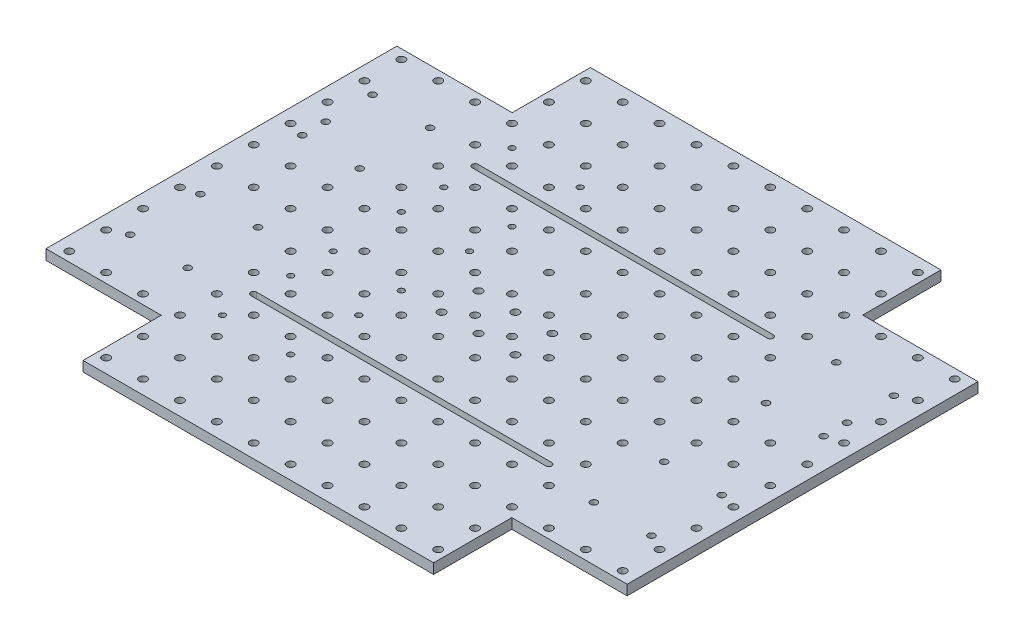
SolidWorks part; units mm, degrees
ref_plane "Front Plane" through (0, 0, 0) normal (0, 0, 1) x (1, 0, 0)
ref_plane "Top Plane" through (0, 0, 0) normal (0, 1, 0) x (1, 0, 0)
ref_plane "Right Plane" through (0, 0, 0) normal (1, 0, 0) x (0, 0, -1)
sketch "Sketch1" plane through (0, 0, 0) normal (0, 1, 0) x (1, 0, 0)
  line L0 (95, -95.1) -> (157.5, -95.1)
  line L1 (-157.5, 95.1) -> (-95, 95.1)
  line L2 (-157.5, 95.1) -> (-157.5, -95.1)
  line L3 (-157.5, -95.1) -> (-95, -95.1)
  line L4 (157.5, 95.1) -> (157.5, -95.1)
  line L5 (-157.5, 95.1) -> (157.5, -95.1) construction
  line L6 (-157.5, -95.1) -> (157.5, 95.1) construction
  line L7 (95, 137.5) -> (-95, 137.5)
  line L8 (95, 137.5) -> (95, 95.1)
  line L9 (95, -137.5) -> (-95, -137.5)
  line L10 (-95, 137.5) -> (-95, 95.1)
  line L11 (95, 137.5) -> (-95, -137.5) construction
  line L12 (95, -137.5) -> (-95, 137.5) construction
  line L13 (95, -95.1) -> (95, -137.5)
  line L14 (-95, -95.1) -> (-95, -137.5)
  line L15 (95, 95.1) -> (157.5, 95.1)
  point P0 (0, 0)
  point P6 (0, 0)
  dimension "D1" = 315
  dimension "D2" = 42.4
  dimension "D3" = 275
  dimension "D4" = 190
extrude "Boss-Extrude1" add sketch "Sketch1" along normal blind 5.4864
sketch "Sketch2" plane through (0, 5.4864, 0) normal (0, 1, 0) x (1, 0, 0)
  line L0 (0, 0) -> (150, 0) construction
  line L1 (150, 0) -> (150, -130) construction
  line L2 (150, -130) -> (130, -130) construction
  line L3 (150, -110) -> (130, -110) construction
  line L4 (150, -90) -> (130, -90) construction
  line L5 (150, -70) -> (130, -70) construction
  line L6 (150, -50) -> (130, -50) construction
  line L7 (150, -30) -> (130, -30) construction
  line L8 (150, -10) -> (130, -10) construction
  line L9 (150, 10) -> (130, 10) construction
  line L10 (150, 30) -> (130, 30) construction
  line L11 (150, 50) -> (130, 50) construction
  line L12 (150, 70) -> (130, 70) construction
  line L13 (150, 90) -> (130, 90) construction
  line L14 (150, 110) -> (130, 110) construction
  line L15 (150, -130) -> (150, -110) construction
  line L16 (150, 130) -> (130, 130) construction
  line L17 (150, 150) -> (130, 150) construction
  circle A0 centre (150, -130) radius 2.1 construction
  circle A1 centre (130, -130) radius 2.1 construction
  circle A2 centre (110, -130) radius 2.1 construction
  circle A3 centre (90, -130) radius 2.1
  circle A4 centre (70, -130) radius 2.1
  circle A5 centre (50, -130) radius 2.1
  circle A6 centre (30, -130) radius 2.1
  circle A7 centre (10, -130) radius 2.1
  circle A8 centre (-10, -130) radius 2.1
  circle A9 centre (-30, -130) radius 2.1
  circle A10 centre (-50, -130) radius 2.1
  circle A11 centre (-70, -130) radius 2.1
  circle A12 centre (-90, -130) radius 2.1
  circle A13 centre (-110, -130) radius 2.1
  circle A14 centre (-130, -130) radius 2.1 construction
  circle A15 centre (-150, -130) radius 2.1 construction
  circle A17 centre (150, -110) radius 2.1 construction
  circle A18 centre (130, -110) radius 2.1 construction
  circle A19 centre (110, -110) radius 2.1 construction
  circle A20 centre (90, -110) radius 2.1
  circle A21 centre (70, -110) radius 2.1
  circle A22 centre (50, -110) radius 2.1
  circle A23 centre (30, -110) radius 2.1
  circle A24 centre (10, -110) radius 2.1
  circle A25 centre (-10, -110) radius 2.1
  circle A26 centre (-30, -110) radius 2.1
  circle A27 centre (-50, -110) radius 2.1
  circle A28 centre (-70, -110) radius 2.1
  circle A29 centre (-90, -110) radius 2.1
  circle A30 centre (-110, -110) radius 2.1
  circle A31 centre (-130, -110) radius 2.1 construction
  circle A32 centre (-150, -110) radius 2.1 construction
  circle A34 centre (150, -90) radius 2.1
  circle A35 centre (130, -90) radius 2.1
  circle A36 centre (110, -90) radius 2.1
  circle A37 centre (90, -90) radius 2.1
  circle A38 centre (70, -90) radius 2.1
  circle A39 centre (50, -90) radius 2.1
  circle A40 centre (30, -90) radius 2.1
  circle A41 centre (10, -90) radius 2.1
  circle A42 centre (-10, -90) radius 2.1
  circle A43 centre (-30, -90) radius 2.1
  circle A44 centre (-50, -90) radius 2.1
  circle A45 centre (-70, -90) radius 2.1
  circle A46 centre (-90, -90) radius 2.1
  circle A47 centre (-110, -90) radius 2.1
  circle A48 centre (-130, -90) radius 2.1
  circle A49 centre (-150, -90) radius 2.1
  circle A51 centre (150, -70) radius 2.1
  circle A52 centre (130, -70) radius 2.1 construction
  circle A53 centre (110, -70) radius 2.1 construction
  circle A54 centre (90, -70) radius 2.1
  circle A55 centre (70, -70) radius 2.1
  circle A56 centre (50, -70) radius 2.1
  circle A57 centre (30, -70) radius 2.1
  circle A58 centre (10, -70) radius 2.1
  circle A59 centre (-10, -70) radius 2.1
  circle A60 centre (-30, -70) radius 2.1
  circle A61 centre (-50, -70) radius 2.1
  circle A62 centre (-70, -70) radius 2.1
  circle A63 centre (-90, -70) radius 2.1
  circle A64 centre (-110, -70) radius 2.1 construction
  circle A65 centre (-130, -70) radius 2.1 construction
  circle A66 centre (-150, -70) radius 2.1
  circle A68 centre (150, -50) radius 2.1
  circle A69 centre (130, -50) radius 2.1 construction
  circle A70 centre (110, -50) radius 2.1 construction
  circle A71 centre (90, -50) radius 2.1
  circle A72 centre (70, -50) radius 2.1
  circle A73 centre (50, -50) radius 2.1
  circle A74 centre (30, -50) radius 2.1
  circle A75 centre (10, -50) radius 2.1
  circle A76 centre (-10, -50) radius 2.1
  circle A77 centre (-30, -50) radius 2.1
  circle A78 centre (-50, -50) radius 2.1
  circle A79 centre (-70, -50) radius 2.1
  circle A80 centre (-90, -50) radius 2.1
  circle A81 centre (-110, -50) radius 2.1 construction
  circle A82 centre (-130, -50) radius 2.1 construction
  circle A83 centre (-150, -50) radius 2.1
  circle A85 centre (150, -30) radius 2.1
  circle A86 centre (130, -30) radius 2.1 construction
  circle A87 centre (110, -30) radius 2.1 construction
  circle A88 centre (90, -30) radius 2.1
  circle A89 centre (70, -30) radius 2.1
  circle A90 centre (50, -30) radius 2.1
  circle A91 centre (30, -30) radius 2.1
  circle A92 centre (10, -30) radius 2.1
  circle A93 centre (-10, -30) radius 2.1
  circle A94 centre (-30, -30) radius 2.1
  circle A95 centre (-50, -30) radius 2.1
  circle A96 centre (-70, -30) radius 2.1
  circle A97 centre (-90, -30) radius 2.1
  circle A98 centre (-110, -30) radius 2.1 construction
  circle A99 centre (-130, -30) radius 2.1 construction
  circle A100 centre (-150, -30) radius 2.1
  circle A102 centre (150, -10) radius 2.1
  circle A103 centre (130, -10) radius 2.1
  circle A104 centre (110, -10) radius 2.1
  circle A105 centre (90, -10) radius 2.1
  circle A106 centre (70, -10) radius 2.1
  circle A107 centre (50, -10) radius 2.1
  circle A108 centre (30, -10) radius 2.1
  circle A109 centre (10, -10) radius 2.1
  circle A110 centre (-10, -10) radius 2.1
  circle A111 centre (-30, -10) radius 2.1
  circle A112 centre (-50, -10) radius 2.1
  circle A113 centre (-70, -10) radius 2.1
  circle A114 centre (-90, -10) radius 2.1
  circle A115 centre (-110, -10) radius 2.1
  circle A116 centre (-130, -10) radius 2.1
  circle A117 centre (-150, -10) radius 2.1
  circle A119 centre (150, 10) radius 2.1
  circle A120 centre (130, 10) radius 2.1
  circle A121 centre (110, 10) radius 2.1
  circle A122 centre (90, 10) radius 2.1
  circle A123 centre (70, 10) radius 2.1
  circle A124 centre (50, 10) radius 2.1
  circle A125 centre (30, 10) radius 2.1
  circle A126 centre (10, 10) radius 2.1
  circle A127 centre (-10, 10) radius 2.1
  circle A128 centre (-30, 10) radius 2.1
  circle A129 centre (-50, 10) radius 2.1
  circle A130 centre (-70, 10) radius 2.1
  circle A131 centre (-90, 10) radius 2.1
  circle A132 centre (-110, 10) radius 2.1
  circle A133 centre (-130, 10) radius 2.1
  circle A134 centre (-150, 10) radius 2.1
  circle A136 centre (150, 30) radius 2.1
  circle A137 centre (130, 30) radius 2.1 construction
  circle A138 centre (110, 30) radius 2.1 construction
  circle A139 centre (90, 30) radius 2.1
  circle A140 centre (70, 30) radius 2.1
  circle A141 centre (50, 30) radius 2.1
  circle A142 centre (30, 30) radius 2.1
  circle A143 centre (10, 30) radius 2.1
  circle A144 centre (-10, 30) radius 2.1
  circle A145 centre (-30, 30) radius 2.1
  circle A146 centre (-50, 30) radius 2.1
  circle A147 centre (-70, 30) radius 2.1
  circle A148 centre (-90, 30) radius 2.1
  circle A149 centre (-110, 30) radius 2.1 construction
  circle A150 centre (-130, 30) radius 2.1 construction
  circle A151 centre (-150, 30) radius 2.1
  circle A153 centre (150, 50) radius 2.1
  circle A154 centre (130, 50) radius 2.1 construction
  circle A155 centre (110, 50) radius 2.1 construction
  circle A156 centre (90, 50) radius 2.1
  circle A157 centre (70, 50) radius 2.1
  circle A158 centre (50, 50) radius 2.1
  circle A159 centre (30, 50) radius 2.1
  circle A160 centre (10, 50) radius 2.1
  circle A161 centre (-10, 50) radius 2.1
  circle A162 centre (-30, 50) radius 2.1
  circle A163 centre (-50, 50) radius 2.1
  circle A164 centre (-70, 50) radius 2.1
  circle A165 centre (-90, 50) radius 2.1
  circle A166 centre (-110, 50) radius 2.1 construction
  circle A167 centre (-130, 50) radius 2.1 construction
  circle A168 centre (-150, 50) radius 2.1
  circle A170 centre (150, 70) radius 2.1
  circle A171 centre (130, 70) radius 2.1 construction
  circle A172 centre (110, 70) radius 2.1 construction
  circle A173 centre (90, 70) radius 2.1
  circle A174 centre (70, 70) radius 2.1
  circle A175 centre (50, 70) radius 2.1
  circle A176 centre (30, 70) radius 2.1
  circle A177 centre (10, 70) radius 2.1
  circle A178 centre (-10, 70) radius 2.1
  circle A179 centre (-30, 70) radius 2.1
  circle A180 centre (-50, 70) radius 2.1
  circle A181 centre (-70, 70) radius 2.1
  circle A182 centre (-90, 70) radius 2.1
  circle A183 centre (-110, 70) radius 2.1 construction
  circle A184 centre (-130, 70) radius 2.1 construction
  circle A185 centre (-150, 70) radius 2.1
  circle A187 centre (150, 90) radius 2.1
  circle A188 centre (130, 90) radius 2.1
  circle A189 centre (110, 90) radius 2.1
  circle A190 centre (90, 90) radius 2.1
  circle A191 centre (70, 90) radius 2.1
  circle A192 centre (50, 90) radius 2.1
  circle A193 centre (30, 90) radius 2.1
  circle A194 centre (10, 90) radius 2.1
  circle A195 centre (-10, 90) radius 2.1
  circle A196 centre (-30, 90) radius 2.1
  circle A197 centre (-50, 90) radius 2.1
  circle A198 centre (-70, 90) radius 2.1
  circle A199 centre (-90, 90) radius 2.1
  circle A200 centre (-110, 90) radius 2.1
  circle A201 centre (-130, 90) radius 2.1
  circle A202 centre (-150, 90) radius 2.1
  circle A204 centre (150, 110) radius 2.1
  circle A205 centre (130, 110) radius 2.1
  circle A206 centre (110, 110) radius 2.1
  circle A207 centre (90, 110) radius 2.1
  circle A208 centre (70, 110) radius 2.1
  circle A209 centre (50, 110) radius 2.1
  circle A210 centre (30, 110) radius 2.1
  circle A211 centre (10, 110) radius 2.1
  circle A212 centre (-10, 110) radius 2.1
  circle A213 centre (-30, 110) radius 2.1
  circle A214 centre (-50, 110) radius 2.1
  circle A215 centre (-70, 110) radius 2.1
  circle A216 centre (-90, 110) radius 2.1
  circle A217 centre (-110, 110) radius 2.1
  circle A218 centre (-130, 110) radius 2.1
  circle A219 centre (-150, 110) radius 2.1
  circle A221 centre (150, 130) radius 2.1 construction
  circle A222 centre (130, 130) radius 2.1 construction
  circle A223 centre (110, 130) radius 2.1
  circle A224 centre (90, 130) radius 2.1
  circle A225 centre (70, 130) radius 2.1
  circle A226 centre (50, 130) radius 2.1
  circle A227 centre (30, 130) radius 2.1
  circle A228 centre (10, 130) radius 2.1
  circle A229 centre (-10, 130) radius 2.1
  circle A230 centre (-30, 130) radius 2.1
  circle A231 centre (-50, 130) radius 2.1
  circle A232 centre (-70, 130) radius 2.1
  circle A233 centre (-90, 130) radius 2.1
  circle A234 centre (-110, 130) radius 2.1
  circle A235 centre (-130, 130) radius 2.1 construction
  circle A236 centre (-150, 130) radius 2.1 construction
  circle A238 centre (150, 150) radius 2.1 construction
  circle A239 centre (130, 150) radius 2.1 construction
  circle A240 centre (110, 150) radius 2.1 construction
  circle A241 centre (90, 150) radius 2.1
  circle A242 centre (70, 150) radius 2.1
  circle A243 centre (50, 150) radius 2.1
  circle A244 centre (30, 150) radius 2.1
  circle A245 centre (10, 150) radius 2.1
  circle A246 centre (-10, 150) radius 2.1
  circle A247 centre (-30, 150) radius 2.1
  circle A248 centre (-50, 150) radius 2.1
  circle A249 centre (-70, 150) radius 2.1
  circle A250 centre (-90, 150) radius 2.1
  circle A251 centre (-110, 150) radius 2.1
  circle A252 centre (-130, 150) radius 2.1 construction
  circle A253 centre (-150, 150) radius 2.1 construction
  dimension "D3" = 4.2
  dimension "D1" = 150
  dimension "D2" = 130
  dimension "D5" = 20
  dimension "D7" = 20
  dimension "D4" = 16
  dimension "D6" = 15
extrude "Cut-Extrude1" cut sketch "Sketch2" against normal through all
hole_wizard "Ø3.0mm Clearance Dowel Hole1" positions "Sketch3" profile "Sketch4" hole size "Ø3.0" standard "ANSI Metric" end condition through all
sketch "Sketch3" plane through (-115.8567, 5.4864, -238.7408) normal (0, 1, 0) x (1, 0, 0)
  point P0 (-25.4433, -173.0408)
  point P3 (5.7567, -173.0408)
  point P6 (-25.4433, -211.1408)
  point P9 (5.7567, -211.1408)
  point P12 (225.9567, -173.0408)
  point P15 (257.1567, -173.0408)
  point P18 (225.9567, -211.1408)
  point P21 (257.1567, -211.1408)
  point P24 (225.9567, -304.4408)
  point P27 (225.9567, -266.3408)
  point P30 (257.1567, -266.3408)
  point P33 (257.1567, -304.4408)
  point P36 (-25.4433, -266.3408)
  point P39 (-25.4433, -304.4408)
  point P42 (5.7567, -304.4408)
  point P45 (5.7567, -266.3408)
  point P48 (-25.4433, -198.4408)
  point P51 (257.1567, -198.4408)
sketch "Sketch4" plane through (-141.3, 5.4864, -65.7) normal (1, 0, 0) x (0, 0, 1)
  line L0 (0, 0) -> (0, 5.4864)
  line L1 (0, 5.4864) -> (1.85, 5.4864)
  line L2 (1.85, 5.4864) -> (1.85, 0)
  line L3 (1.85, 0) -> (0, 0)
  line L4 (0, -6.35) -> (0, 107.95) construction
  dimension "Thru Hole Dia." = 3.7
  dimension "Thru Hole Depth" = 5.4864
sketch "Sketch5" plane through (0, 5.4864, 0) normal (0, 1, 0) x (1, 0, 0)
  line L0 (-30, 130) -> (-10, 130) construction
  line L1 (-10, 130) -> (-20.47, 130) construction
  line L2 (-20.47, 130) -> (-20.47, 2.3) construction
  line L3 (-20.47, 2.3) -> (-0.47, 2.3) construction
  line L4 (-20.47, -17.7) -> (-0.47, -17.7) construction
  line L5 (-20.47, 2.3) -> (-20.47, -17.7) construction
  circle A0 centre (-20.47, 2.3) radius 2.1
  circle A1 centre (-0.47, 2.3) radius 2.1
  circle A2 centre (19.53, 2.3) radius 2.1
  circle A3 centre (-20.47, -17.7) radius 2.1
  circle A4 centre (-0.47, -17.7) radius 2.1
  circle A5 centre (19.53, -17.7) radius 2.1
  point P5 (0, 0)
  point P24 (0, 0)
  point P26 (-10, 130)
  point P28 (-30, 130)
  point P30 (0, 0)
  point P31 (-25.9558, 130)
  point P32 (-21.4321, 130)
  dimension "D2" = 4.2
  dimension "D1" = 127.7
  dimension "D4" = 20
  dimension "D6" = 20
  dimension "D7" = 9.53
  dimension "D3" = 3
  dimension "D5" = 2
extrude "Cut-Extrude2" cut sketch "Sketch5" against normal through all
sketch "Sketch6" plane through (0, 5.4864, 0) normal (0, 1, 0) x (1, 0, 0)
  line L0 (-80, 60) -> (80, 60) construction
  line L1 (-80, -60) -> (80, -60) construction
  line L2 (-80, -60) -> (-80, 60) construction
  line L3 (-80, 60) -> (80, 60) construction
  line L4 (80, -60) -> (80, 60) construction
  line L5 (-80, -60) -> (80, 60) construction
  line L6 (-80, 60) -> (80, -60) construction
  line L7 (-80, 61.6) -> (80, 61.6)
  line L8 (-80, 58.4) -> (80, 58.4)
  line L9 (-80, -60) -> (80, -60) construction
  line L10 (-80, -58.4) -> (80, -58.4)
  line L11 (-80, -61.6) -> (80, -61.6)
  arc A0 (-80, 61.6) -> (-80, 58.4) centre (-80, 60) ccw
  arc A1 (80, 58.4) -> (80, 61.6) centre (80, 60) ccw
  arc A2 (-80, -58.4) -> (-80, -61.6) centre (-80, -60) ccw
  arc A3 (80, -61.6) -> (80, -58.4) centre (80, -60) ccw
  point P0 (0, 0)
  point P6 (0, 60)
  point P11 (0, -60)
  dimension "D1" = 120
  dimension "D2" = 160
  dimension "D3" = 3.2
extrude "Cut-Extrude3" cut sketch "Sketch6" against normal through all
sketch "Sketch7" plane through (0, 5.4864, 0) normal (0, 1, 0) x (1, 0, 0)
  line L0 (-78.475, 41.525) -> (-41.525, 41.525) construction
  line L1 (-78.475, -18.475) -> (-41.525, -18.475) construction
  line L2 (-78.475, -18.475) -> (-78.475, 18.475) construction
  line L3 (-78.475, 18.475) -> (-41.525, 18.475) construction
  line L4 (-41.525, -18.475) -> (-41.525, 18.475) construction
  line L5 (-78.475, -18.475) -> (-41.525, 18.475) construction
  line L6 (-78.475, 18.475) -> (-41.525, -18.475) construction
  line L7 (-78.475, 41.525) -> (-78.475, 78.475) construction
  line L8 (-78.475, 78.475) -> (-41.525, 78.475) construction
  line L9 (-41.525, 41.525) -> (-41.525, 78.475) construction
  line L10 (-78.475, 41.525) -> (-41.525, 78.475) construction
  line L11 (-78.475, 78.475) -> (-41.525, 41.525) construction
  line L12 (-78.475, -78.475) -> (-41.525, -78.475) construction
  line L13 (-78.475, -78.475) -> (-78.475, -41.525) construction
  line L14 (-78.475, -41.525) -> (-41.525, -41.525) construction
  line L15 (-41.525, -78.475) -> (-41.525, -41.525) construction
  line L16 (-78.475, -78.475) -> (-41.525, -41.525) construction
  line L17 (-78.475, -41.525) -> (-41.525, -78.475) construction
  line L18 (-60, 60) -> (-60, -60) construction
  line L21 (-157.5, 0) -> (157.5, 0) construction
  line L22 (-157.5, 95.1) -> (-157.5, -95.1) construction
  line L23 (157.5, -95.1) -> (157.5, 95.1) construction
  line L24 (-70, 70) -> (-50, 70) construction
  line L25 (-60, 70) -> (-60, 78.475) construction
  circle A0 centre (-78.475, 18.475) radius 1.6
  circle A1 centre (-78.475, -18.475) radius 1.6
  circle A2 centre (-41.525, -18.475) radius 1.6
  circle A3 centre (-41.525, 18.475) radius 1.6
  circle A4 centre (-78.475, 78.475) radius 1.6
  circle A5 centre (-78.475, 41.525) radius 1.6
  circle A6 centre (-41.525, 41.525) radius 1.6
  circle A7 centre (-41.525, 78.475) radius 1.6
  circle A8 centre (-78.475, -41.525) radius 1.6
  circle A9 centre (-78.475, -78.475) radius 1.6
  circle A10 centre (-41.525, -78.475) radius 1.6
  circle A11 centre (-41.525, -41.525) radius 1.6
  point P0 (-60, 0)
  point P9 (-60, 60)
  point P18 (-60, -60)
  point P27 (-60, -52.9419)
  point P35 (-60, 0)
  dimension "D1" = 3.2
  dimension "D2" = 36.95
  dimension "D3" = 36.95
  dimension "D4" = 36.95
  dimension "D5" = 60
extrude "Cut-Extrude4" cut sketch "Sketch7" against normal through all
